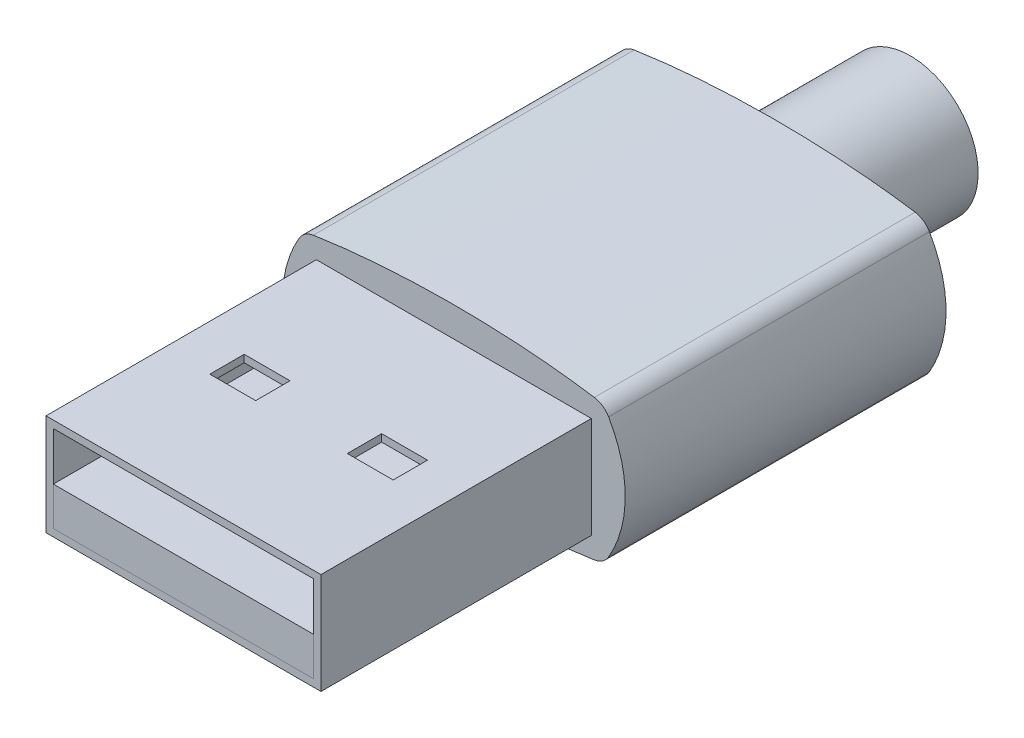
SolidWorks part; units mm, degrees
ref_plane "Front" through (0, 0, 0) normal (0, 0, 1) x (1, 0, 0)
ref_plane "Top" through (0, 0, 0) normal (0, 1, 0) x (1, 0, 0)
ref_plane "Right" through (0, 0, 0) normal (1, 0, 0) x (0, 0, -1)
sketch "Sketch1" plane through (0, 0, 0) normal (0, 0, 1) x (1, 0, 0)
  line L0 (-5.68, 1.89) -> (5.68, 1.89)
  line L1 (-6, 2.21) -> (6, 2.21)
  line L2 (-6, 2.21) -> (-6, -2.21)
  line L3 (-6, -2.21) -> (6, -2.21)
  line L4 (6, 2.21) -> (6, -2.21)
  line L5 (-6, 2.21) -> (6, -2.21) construction
  line L6 (-6, -2.21) -> (6, 2.21) construction
  line L7 (5.68, 1.89) -> (5.68, -1.89)
  line L8 (-5.68, -1.89) -> (5.68, -1.89)
  line L9 (-5.68, 1.89) -> (-5.68, -1.89)
  line L10 (-5.68, -0.21) -> (5.68, -0.21)
  point P0 (0, 0)
  dimension "D1" = 12
  dimension "D2" = 4.42
  dimension "D4" = 2
  dimension "D3" = 0.32
extrude "Boss-Extrude1" add sketch "Sketch1" against normal blind 11.8 contours L4 L1 L2 L3 L9 L0 L7 L8 | L10 L9 L8 L7 region at (0, -1.05, 0) region at (0, 2.0821, 0)
split line "Split Line1"
sketch "Sketch1<4>" plane through (0, 0, 0) normal (0, 0, 1) x (1, 0, 0) same geometry as "Sketch1"
sketch "Sketch2" plane through (0, 0, -11.8) normal (0, 0, -1) x (-1, 0, 0)
  line L0 (6, 2.21) -> (6, -2.21) construction
  line L1 (6, -2.21) -> (-6, -2.21) construction
  line L2 (-2.8261, -6.6161) -> (6.6161, 2.8261) construction
  line L3 (6, 2.21) -> (-6, 2.21) construction
  line L4 (-6, -2.21) -> (-2.21, -6) construction
  line L5 (-6.6161, -2.8261) -> (-2.8261, -6.6161) construction
  arc A0 (-6.1321, 3.0712) -> (-6.7544, 2.646) centre (-6, 2.21) ccw
  arc A1 (-6.7544, -2.646) -> (-6.1321, -3.0712) centre (-6, -2.21) ccw
  arc A2 (6.1321, -3.0712) -> (6.7544, -2.646) centre (6, -2.21) ccw
  arc A3 (6.7544, 2.646) -> (6.1321, 3.0712) centre (6, 2.21) ccw
  ellipse E0 centre (0, 0) end of major axis (-12.6659, 0) minor radius 3.51 (-6.1321, -3.0712) -> (6.1321, -3.0712) ccw
  ellipse E1 centre (0, 0) end of major axis (-7.48, 0) minor radius 6.1583 (6.7544, -2.646) -> (6.7544, 2.646) ccw
  ellipse E2 centre (0, 0) end of major axis (-12.6659, 0) minor radius 3.51 (6.1321, 3.0712) -> (-6.1321, 3.0712) ccw
  ellipse E3 centre (0, 0) end of major axis (-7.48, 0) minor radius 6.1583 (-6.7544, 2.646) -> (-6.7544, -2.646) ccw
  point P1 (-6.5269, -3.0081)
  point P13 (6.5269, -3.0081)
  point P14 (6.5269, 3.0081)
  point P16 (-6.5269, 3.0081)
  point P50 (-2.8635, -6.6535)
  point P52 (-2.5987, -6.3887)
  dimension "D1" = 7.02
  dimension "D2" = 14.96
  dimension "D3" = 135
  dimension "D4" = 13.3533
extrude "Boss-Extrude3" add sketch "Sketch2" along normal blind 14
sketch "Sketch3" plane through (0, 0, -25.8) normal (0, 0, -1) x (-1, 0, 0)
  circle A0 centre (0, 0) radius 2.96
  dimension "D1" = 5.92
extrude "Boss-Extrude4" add sketch "Sketch3" along normal blind 5.92
sketch "Sketch4" plane through (0, 2.21, 0) normal (0, 1, 0) x (1, 0, 0)
  line L0 (-6, 0) -> (6, 0) construction
  line L1 (2, 5.15) -> (2, 6.65)
  line L2 (4, 6.65) -> (2, 6.65)
  line L3 (-6, 11.8) -> (0, 11.8) construction
  line L8 (-6, 11.8) -> (-6, 0) construction
  line L9 (-6, 0) -> (0, 0) construction
  line L10 (0, 11.8) -> (0, 0) construction
  line L11 (-6, 11.8) -> (0, 0) construction
  line L12 (-6, 0) -> (0, 11.8) construction
  line L13 (-6, 11.8) -> (-6, 0) construction
  line L14 (-6, 11.8) -> (6, 11.8) construction
  line L15 (4, 5.15) -> (4, 6.65)
  line L16 (-4, 5.15) -> (-2, 5.15)
  line L17 (-4, 5.15) -> (-4, 6.65)
  line L18 (-4, 6.65) -> (-2, 6.65)
  line L19 (-2, 5.15) -> (-2, 6.65)
  line L20 (-4, 5.15) -> (-2, 6.65) construction
  line L21 (-4, 6.65) -> (-2, 5.15) construction
  line L22 (4, 5.15) -> (2, 5.15)
  point P0 (-3, 5.9)
  point P13 (-3, 5.9)
  dimension "D1" = 2
  dimension "D2" = 1.5
extrude "Cut-Extrude1" cut sketch "Sketch4" against normal up to next
